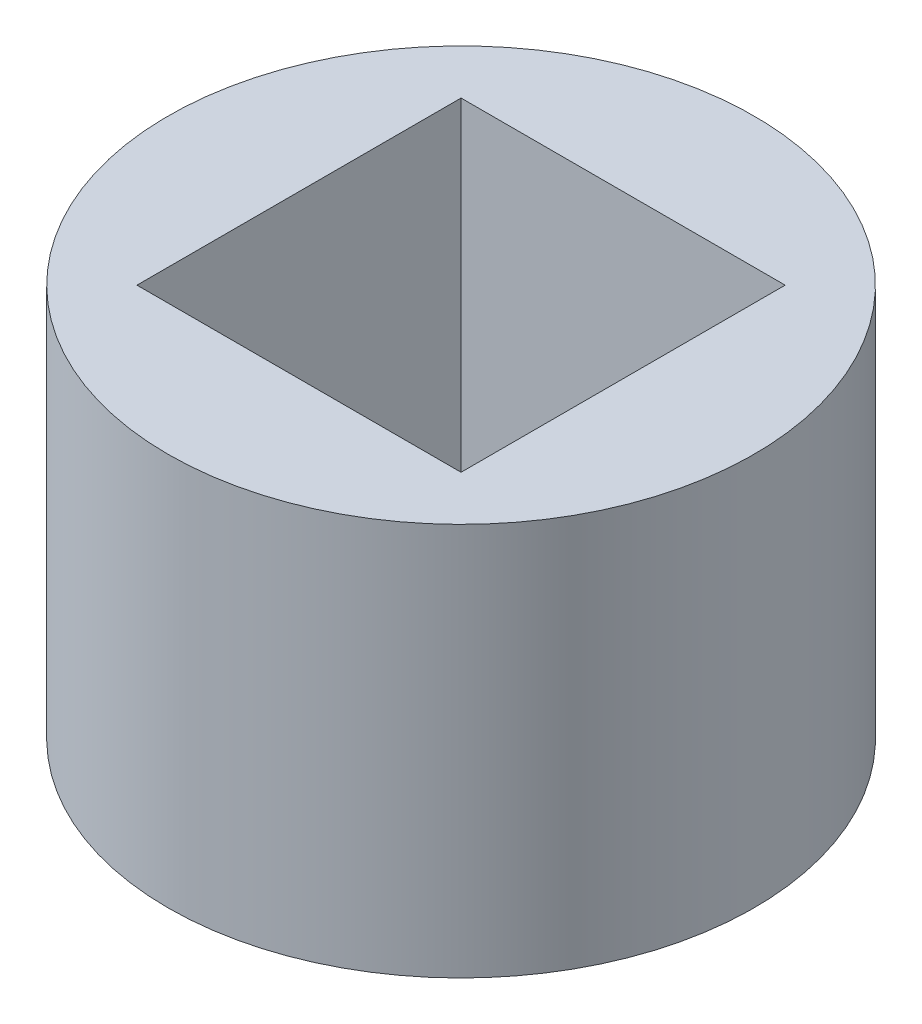
SolidWorks part; units mm, degrees
ref_plane "Front Plane" through (0, 0, 0) normal (0, 0, 1) x (1, 0, 0)
ref_plane "Top Plane" through (0, 0, 0) normal (0, 1, 0) x (1, 0, 0)
ref_plane "Right Plane" through (0, 0, 0) normal (1, 0, 0) x (0, 0, -1)
sketch "Sketch1" plane through (0, 0, 0) normal (0, 1, 0) x (1, 0, 0)
  line L1 (-4.95, -4.95) -> (4.95, -4.95)
  line L2 (-4.95, -4.95) -> (-4.95, 4.95)
  line L3 (-4.95, 4.95) -> (4.95, 4.95)
  line L4 (4.95, -4.95) -> (4.95, 4.95)
  line L5 (-4.95, -4.95) -> (4.95, 4.95) construction
  line L6 (-4.95, 4.95) -> (4.95, -4.95) construction
  circle A1 centre (0, 0) radius 8.95
  dimension "D1" = 9.9
  dimension "D3" = 17.9
  dimension "D2" = 9.9
  dimension "D4" = 0
extrude "Boss-Extrude1" add sketch "Sketch1" along normal blind 12
